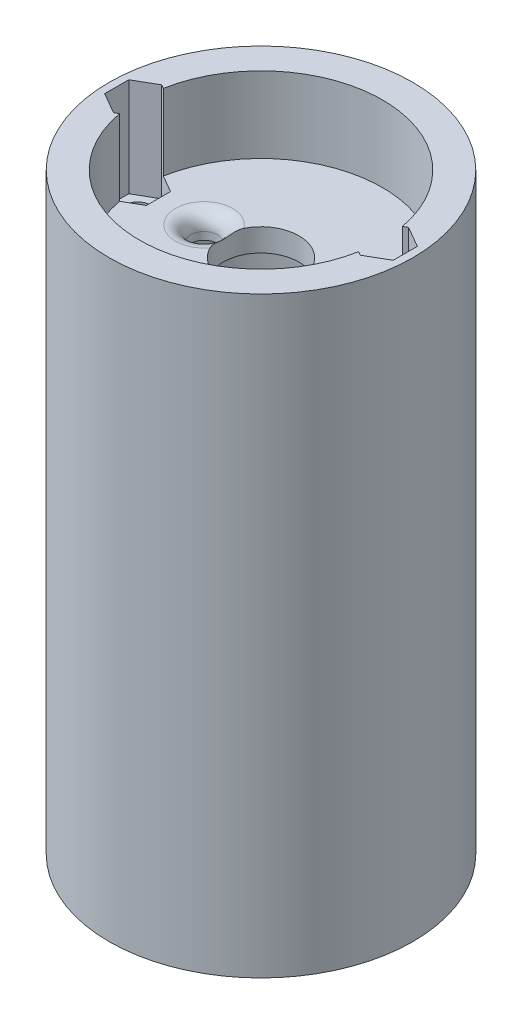
SolidWorks part; units mm, degrees
ref_plane "Front Plane" through (0, 0, 0) normal (0, 0, 1) x (1, 0, 0)
ref_plane "Top Plane" through (0, 0, 0) normal (0, 1, 0) x (1, 0, 0)
ref_plane "Right Plane" through (0, 0, 0) normal (1, 0, 0) x (0, 0, -1)
sketch "Sketch1" plane through (0, 0, 0) normal (0, 1, 0) x (1, 0, 0)
  circle A0 centre (0, 0) radius 16
  circle A1 centre (0, 0) radius 20
  circle A2 centre (0, 0) radius 6
  dimension "D1" = 32
  dimension "D2" = 40
  dimension "D3" = 12
extrude "Boss-Extrude1" add sketch "Sketch1" along normal blind 10 contours A1 A0 region at (-19.4343, 0, 0)
sketch "Sketch2" plane through (0, 0, 0) normal (0, -1, 0) x (-1, 0, 0)
  line L0 (-10.25, 0) -> (-20, 0)
  line L1 (10.25, 0) -> (20, 0)
  line L2 (-10.25, 2) -> (-20, 2)
  line L3 (10.25, -2) -> (20, -2)
  line L4 (-10.25, -2) -> (-20, -2)
  line L5 (10.25, 2) -> (20, 2)
  line L6 (20, -2) -> (9.3875, -2)
  line L7 (0, 0) -> (-2.3286, 0)
  line L8 (-20, -2) -> (-9.3875, -2)
  line L9 (-20, 2) -> (-9.3875, 2)
  line L10 (10.25, 2) -> (9.3875, 2)
  circle A0 centre (0, 0) radius 7.5
  circle A1 centre (-7.5, 0) radius 1.75
  circle A2 centre (7.5, 0) radius 1.75
  circle A3 centre (7.5, 0) radius 2.75
  circle A4 centre (-7.5, 0) radius 2.75
  circle A5 centre (0, 0) radius 12.5
  circle A6 centre (0, 0) radius 20
  circle A7 centre (0, 0) radius 16
  dimension "D1" = 15
  dimension "D2" = 3.5
  dimension "D3" = 5.5
  dimension "D4" = 25
  dimension "D5" = 7.5
  dimension "D6" = 2
  dimension "D7" = 2
extrude "Boss-Extrude2" add sketch "Sketch2" along normal blind 3 separate body contours L3 A5 L1 A3 L6 | L6 A6 L1 A5 | L1 A6 L5 A5 | L1 A5 L5 L10 A3 | A0 A3 A2 | A0 A3 A2 | A0 A4 A1 | A4 A0 A1 | L0 A5 L4 L8 A4 | L0 A6 L8 A5 | L9 A6 L0 A5 | L2 A5 L0 A4 L9 region at (11.2027, 0, 1.0451) region at (11.2027, 0, -1.0451) region at (9.9665, 0, -1.0637) region at (14.2022, 0, 1.0017) region at (14.2022, 0, -1.0017) region at (5.4307, 0, -1.7191) region at (-11.2027, 0, -1.0451) region at (-14.2022, 0, -1.0017) region at (-14.2022, 0, 1.0017) region at (-11.2027, 0, 1.0451) region at (-8.2579, 0, -2.577) region at (-7.105, 0, -2.208)
extrude "Boss-Extrude3" add sketch "Sketch2<3>" along normal blind 58 contours L8 A6 L6 A5 | L5 A6 L9 A5 | L1 A6 L5 A5 | L0 A6 L8 A5 | L9 A6 L0 A5 | L6 A6 L1 A5 region at (14.2022, 0, 1.0017) region at (14.2022, 0, -1.0017) region at (14.1067, 0, -2.347) region at (0, 0, 12.847) region at (-14.2022, 0, -1.0017) region at (-14.2022, 0, 1.0017)
sketch "Sketch2<3>" plane through (0, 0, 0) normal (0, -1, 0) x (-1, 0, 0) same geometry as "Sketch2"
fillet "Fillet1" radius 5 4 edges at (-12.339, -1.5, 2) (-12.339, -1.5, -2) (12.339, -1.5, -2) (12.339, -1.5, 2)
sketch "Sketch3" plane through (0, 0, 0) normal (0, -1, 0) x (-1, 0, 0)
  circle A0 centre (0, 0) radius 20
  circle A2 centre (0, 0) radius 14.5
extrude "Boss-Extrude4" add sketch "Sketch3" along normal blind 10
sketch "Sketch4" plane through (0, 0, 0) normal (0, 1, 0) x (1, 0, 0)
  line L1 (-16.25, 3.1754) -> (-19, 1.5877)
  line L2 (-19, 1.5877) -> (-19, -1.5877)
  line L3 (-19, -1.5877) -> (-16.25, -3.1754)
  line L4 (-16.25, -3.1754) -> (-13.5, -1.5877)
  line L5 (-13.5, -1.5877) -> (-13.5, 1.5877)
  line L6 (-13.5, 1.5877) -> (-16.25, 3.1754)
  line L7 (16.25, 3.1754) -> (13.5, 1.5877)
  line L8 (13.5, 1.5877) -> (13.5, -1.5877)
  line L9 (13.5, -1.5877) -> (16.25, -3.1754)
  line L10 (16.25, -3.1754) -> (19, -1.5877)
  line L11 (19, -1.5877) -> (19, 1.5877)
  line L12 (19, 1.5877) -> (16.25, 3.1754)
  circle A0 centre (0, 0) radius 16.25
  circle A1 centre (0, 0) radius 12.5
  arc A2 (9.134, 8.5335) -> (-9.134, 8.5335) centre (0, 0) ccw construction
  circle A3 centre (-16.25, 0) radius 2.75 construction
  circle A4 centre (16.25, 0) radius 2.75 construction
  dimension "D1" = 13.5
  dimension "D2" = 5.5
extrude "Cut-Extrude1" cut sketch "Sketch4" along normal blind 25 contours L1 L2 L3 L4 L5 L6 | L7 L8 L9 L10 L11 L12
extrude "Cut-Extrude2" cut sketch "Sketch4<3>" against normal blind 3 contours L10 L11 L12 L7 L8 L9 | L4 L5 L6 L1 L2 L3
sketch "Sketch4<3>" plane through (0, 0, 0) normal (0, 1, 0) x (1, 0, 0) same geometry as "Sketch4"
sketch "Sketch5" plane through (0, -10, 0) normal (0, -1, 0) x (-1, 0, 0)
  circle A0 centre (0, 0) radius 20
  circle A1 centre (0, 0) radius 12.5
extrude "Boss-Extrude5" add sketch "Sketch5" along normal up to surface (48 mm away) up to face at (0, -58, -16)
sketch "Sketch6" plane through (0, 0, 0) normal (0, 1, 0) x (1, 0, 0)
  circle A0 centre (0, 0) radius 16
  circle A1 centre (-7.5, 0) radius 1.75
  circle A2 centre (7.5, 0) radius 1.75
  circle A3 centre (0, 0) radius 12.5
  circle M10 centre (7.5, 0) radius 1.75
  circle M11 centre (-7.5, 0) radius 1.75
  arc M12 (9.3875, 2) -> (9.3875, -2) centre (7.5, 0) ccw
  arc M13 (9.3875, -2) -> (9.134, -8.5335) centre (5.4804, -5.1201) cw
  arc M14 (9.134, -8.5335) -> (-9.134, -8.5335) centre (0, 0) cw
  arc M15 (-9.134, -8.5335) -> (-9.3875, -2) centre (-5.4804, -5.1201) cw
  arc M16 (-9.3875, -2) -> (-9.3875, 2) centre (-7.5, 0) ccw
  arc M17 (-9.3875, 2) -> (-9.134, 8.5335) centre (-5.4804, 5.1201) cw
  arc M18 (-9.134, 8.5335) -> (9.134, 8.5335) centre (0, 0) cw
  arc M19 (9.134, 8.5335) -> (9.3875, 2) centre (5.4804, 5.1201) cw
extrude "Boss-Extrude7" add sketch "Sketch6" against normal up to surface (3 mm away) contours M12 M19 M18 M17 M16 M15 M14 M13 | A3 M17 M15 M16 M11 | A3 M13 M19 M12 M10 region at (9.725, 0, 0) region at (0, 0, 0) region at (-9.725, 0, 0) up to face at (-7.5, -3, -1.75)
sketch "Sketch7" plane through (0, 0, 0) normal (0, 1, 0) x (1, 0, 0)
  circle A0 centre (0, 0) radius 5
  circle A1 centre (-7.5, 0) radius 2.5
  dimension "D1" = 5
extrude "Cut-Extrude3" cut sketch "Sketch7" against normal up to surface (3 mm away) contours A0 region at (0, 0, 0) up to face at (0, -3, -12.5)
sketch "Sketch9" plane through (0, -3, 0) normal (0, 1, 0) x (1, 0, 0)
  line L0 (-16.25, -3.1754) -> (-16.25, 3.1754)
  line L1 (-19, 0) -> (-13.5, 0)
  line L2 (-19, 1.5877) -> (-19, -1.5877) construction
  line L3 (-13.5, -1.5877) -> (-13.5, 1.5877) construction
  line L4 (0, 5) -> (0, -5)
  circle A0 centre (0, 0) radius 5 construction
  circle A1 centre (-16.25, 0) radius 1.75
  circle A2 centre (16.25, 0) radius 1.75
  dimension "D1" = 3.5
extrude "Cut-Extrude4" cut sketch "Sketch9" against normal through all both and the other way through all contours A1 | A2
sketch "Sketch10" plane through (0, -58, 0) normal (0, -1, 0) x (-1, 0, 0)
  circle A0 centre (0, 0) radius 20
  circle A1 centre (0, 0) radius 18
  circle A2 centre (0, 0) radius 20 construction
  dimension "D1" = 2
extrude "Boss-Extrude8" add sketch "Sketch10" along normal blind 10
fillet "Fillet5" radius 2 2 edges at (-7.5, 0, -1.75) (7.5, 0, -1.75)
sketch "Sketch11" plane through (0, -107.8936, 0) normal (0, 1, 0) x (1, 0, 0)
  line L1 (16.25, 3.1754) -> (13.5, 1.5877)
  line L2 (13.5, 1.5877) -> (13.5, -1.5877)
  line L3 (13.5, -1.5877) -> (16.25, -3.1754)
  line L4 (16.25, -3.1754) -> (19, -1.5877)
  line L5 (19, -1.5877) -> (19, 1.5877)
  line L6 (19, 1.5877) -> (16.25, 3.1754)
  line L7 (-16.25, 3.1754) -> (-19, 1.5877)
  line L8 (-19, 1.5877) -> (-19, -1.5877)
  line L9 (-19, -1.5877) -> (-16.25, -3.1754)
  line L10 (-16.25, -3.1754) -> (-13.5, -1.5877)
  line L11 (-13.5, -1.5877) -> (-13.5, 1.5877)
  line L12 (-13.5, 1.5877) -> (-16.25, 3.1754)
  circle A0 centre (16.25, 0) radius 2.75 construction
  circle A1 centre (-16.25, 0) radius 2.75 construction
extrude "Cut-Extrude5" cut sketch "Sketch11" along normal blind 10 from surface starting at face at (0, -68, -20)
